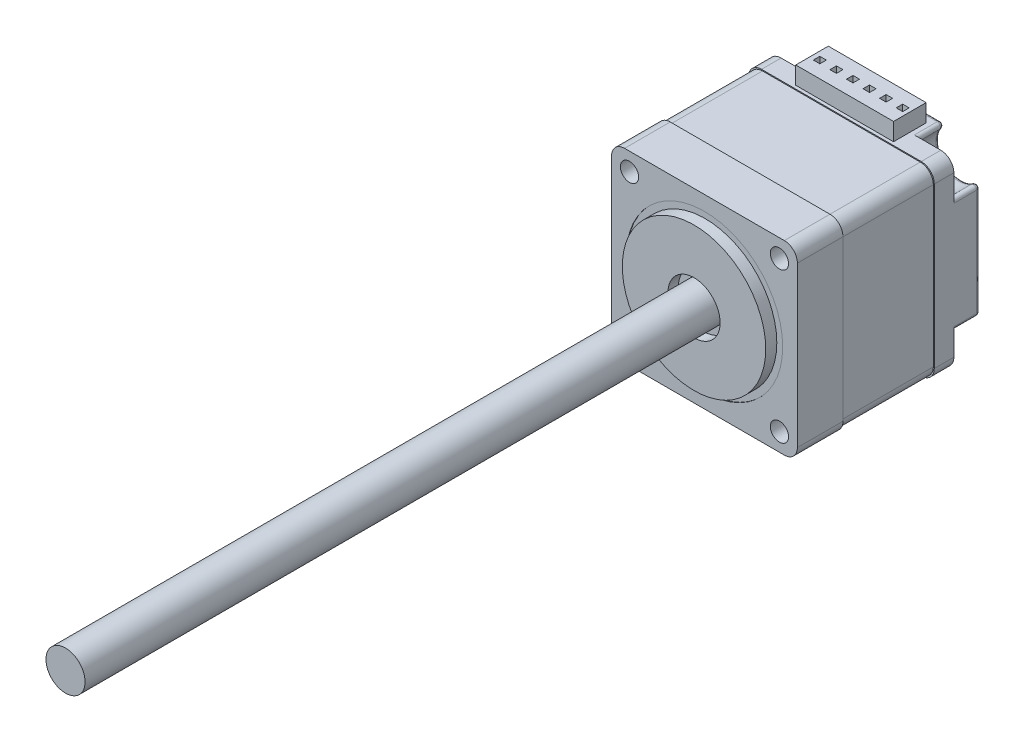
SolidWorks part; units mm, degrees
ref_plane "Front Plane" through (0, 0, 0) normal (0, 0, 1) x (1, 0, 0)
ref_plane "Top Plane" through (0, 0, 0) normal (0, 1, 0) x (1, 0, 0)
ref_plane "Right Plane" through (0, 0, 0) normal (1, 0, 0) x (0, 0, -1)
sketch "Sketch1" plane through (0, 0, 0) normal (0, 0, 1) x (1, 0, 0)
  line L1 (-14.25, 14.25) -> (14.25, 14.25)
  line L2 (-14.25, 14.25) -> (-14.25, -14.25)
  line L3 (-14.25, -14.25) -> (14.25, -14.25)
  line L4 (14.25, 14.25) -> (14.25, -14.25)
  line L5 (-14.25, 14.25) -> (14.25, -14.25) construction
  line L6 (-14.25, -14.25) -> (14.25, 14.25) construction
  point P0 (0, 0)
  dimension "D1" = 28.5
extrude "Boss-Extrude1" add sketch "Sketch1" along normal blind 7
fillet "Fillet1" radius 2 4 edges at (14.25, -14.25, 3.5) (-14.25, -14.25, 3.5) (14.25, 14.25, 3.5) (-14.25, 14.25, 3.5)
sketch "Sketch2" plane through (0, 0, 7) normal (0, 0, 1) x (1, 0, 0)
  circle A0 centre (0, 0) radius 11
  dimension "D1" = 22
extrude "Boss-Extrude2" add sketch "Sketch2" along normal blind 1.6
sketch "Sketch3" plane through (0, 0, 8.6) normal (0, 0, 1) x (1, 0, 0)
  circle A0 centre (0, 0) radius 4
  dimension "D1" = 8
extrude "Cut-Extrude1" cut sketch "Sketch3" against normal blind 1.6
sketch "Sketch4" plane through (0, 0, 7) normal (0, 0, 1) x (1, 0, 0)
  circle A0 centre (0, 0) radius 2.5
  dimension "D1" = 5
extrude "Boss-Extrude3" [suppressed] add sketch "Sketch4" along normal blind 20
sketch "Sketch5" [suppressed] plane through (0, 0, 27) normal (0, 0, 1) x (1, 0, 0)
  line L1 (-2.2, 2) -> (2.2, 2)
  line L2 (-2.2, 2) -> (-2.2, 3)
  line L3 (-2.2, 3) -> (2.2, 3)
  line L4 (2.2, 2) -> (2.2, 3)
  circle A0 centre (0, 0) radius 2.5 construction
  dimension "D1" = 2
  dimension "D2" = 1
  dimension "D3" = 2.2
  dimension "D4" = 4.4
extrude "Cut-Extrude2" [suppressed] cut sketch "Sketch5" against normal blind 20
sketch "Sketch6" plane through (0, 0, 0) normal (0, 0, -1) x (-1, 0, 0)
  line L1 (-14.1, 14.1) -> (14.1, 14.1)
  line L2 (-14.1, 14.1) -> (-14.1, -14.1)
  line L3 (-14.1, -14.1) -> (14.1, -14.1)
  line L4 (14.1, 14.1) -> (14.1, -14.1)
  line L5 (-14.1, 14.1) -> (14.1, -14.1) construction
  line L6 (-14.1, -14.1) -> (14.1, 14.1) construction
  point P0 (0, 0)
  dimension "D1" = 28.2
extrude "Boss-Extrude4" add sketch "Sketch6" along normal blind 14
fillet "Fillet2" radius 2 4 edges at (-14.1, -14.1, -7) (14.1, -14.1, -7) (-14.1, 14.1, -7) (14.1, 14.1, -7)
sketch "Sketch7" plane through (0, 0, -14) normal (0, 0, -1) x (-1, 0, 0)
  line L1 (-14.25, 14.25) -> (14.25, 14.25)
  line L2 (-14.25, 14.25) -> (-14.25, -14.25)
  line L3 (-14.25, -14.25) -> (14.25, -14.25)
  line L4 (14.25, 14.25) -> (14.25, -14.25)
  line L5 (-14.25, 14.25) -> (14.25, -14.25) construction
  line L6 (-14.25, -14.25) -> (14.25, 14.25) construction
  point P0 (0, 0)
  dimension "D1" = 28.5
extrude "Boss-Extrude5" add sketch "Sketch7" along normal blind 7
fillet "Fillet3" radius 2 4 edges at (-14.25, -14.25, -17.5) (14.25, -14.25, -17.5) (-14.25, 14.25, -17.5) (14.25, 14.25, -17.5)
sketch "Sketch8" plane through (0, 14.25, 0) normal (0, 1, 0) x (1, 0, 0)
  line L0 (-12.25, 14) -> (12.25, 14) construction
  line L1 (-7.5, 19.5) -> (7.5, 19.5)
  line L2 (-7.5, 19.5) -> (-7.5, 14.5)
  line L3 (-7.5, 14.5) -> (7.5, 14.5)
  line L4 (7.5, 19.5) -> (7.5, 14.5)
  line L5 (-7.5, 19.5) -> (7.5, 14.5) construction
  line L6 (-7.5, 14.5) -> (7.5, 19.5) construction
  point P0 (0, 17)
  dimension "D1" = 5
  dimension "D2" = 15
  dimension "D3" = 0
  dimension "D4" = 0.5
extrude "Boss-Extrude6" add sketch "Sketch8" along normal blind 2.7
sketch "Sketch9" plane through (0, 0, 7) normal (0, 0, 1) x (1, 0, 0)
  circle A0 centre (-11.5, 11.5) radius 1.4
  circle A1 centre (11.5, 11.5) radius 1.4
  circle A2 centre (11.5, -11.5) radius 1.4
  circle A3 centre (-11.5, -11.5) radius 1.4
  dimension "D1" = 2.8
  dimension "D2" = 23
  dimension "D3" = 23
  dimension "D4" = 23
  dimension "D5" = 23
  dimension "D6" = 11.5
  dimension "D7" = 11.5
  dimension "D8" = 11.5
  dimension "D9" = 11.5
extrude "Cut-Extrude3" cut sketch "Sketch9" against normal blind 42.7
sketch "Sketch10" plane through (0, 0, -21) normal (0, 0, -1) x (-1, 0, 0)
  circle A0 centre (-11.5, 11.5) radius 3.5
  circle A1 centre (11.5, 11.5) radius 3.5
  circle A2 centre (11.5, -11.5) radius 3.5
  circle A3 centre (-11.5, -11.5) radius 3.5
  dimension "D1" = 7
extrude "Cut-Extrude4" cut sketch "Sketch10" against normal blind 4
fillet "Fillet4" radius 0.5 8 edges at (-14.25, 9.3349, -19) (-9.3349, 14.25, -19) (-14.25, -9.3349, -19) (-9.3349, -14.25, -19) (9.3349, -14.25, -19) (14.25, -9.3349, -19) (9.3349, 14.25, -19) (14.25, 9.3349, -19)
fillet "Fillet5" radius 0.5 16 edges at (-13.9839, -8.6348, -21) (-9.0251, -9.0251, -21) (-8.6348, -13.9839, -21) (0, -14.25, -21) (8.6348, -13.9839, -21) (9.0251, -9.0251, -21) (13.9839, -8.6348, -21) (14.25, 0, -21) (13.9839, 8.6348, -21) (9.0251, 9.0251, -21) (8.6348, 13.9839, -21) (0, 14.25, -21) (-8.6348, 13.9839, -21) (-9.0251, 9.0251, -21) (-13.9839, 8.6348, -21) (-14.25, 0, -21)
sketch "Sketch11" plane through (0, 0, 7) normal (0, 0, 1) x (1, 0, 0)
  circle A0 centre (0, 0) radius 11
  circle A1 centre (0, 0) radius 12
  dimension "D1" = 1
extrude "Cut-Extrude5" cut sketch "Sketch11" against normal blind 0.1
sketch "Sketch12" plane through (0, 0, -21) normal (0, 0, -1) x (-1, 0, 0)
  circle A0 centre (0, 0) radius 4
  dimension "D1" = 8
extrude "Cut-Extrude6" cut sketch "Sketch12" against normal blind 2.5
sketch "Sketch13" plane through (0, 0, -18.5) normal (0, 0, -1) x (-1, 0, 0)
  circle A0 centre (0, 0) radius 2.5
  dimension "D1" = 5
extrude "Boss-Extrude7" add sketch "Sketch13" along normal blind 0.5
fillet "Fillet6" radius 0.2 1 edges at (-2.5, 0, -19)
sketch "Sketch14" plane through (0, 16.95, 0) normal (0, 1, 0) x (1, 0, 0)
  line L0 (-7.5, 14.5) -> (7.5, 14.5) construction
  line L1 (-6.8, 17.5) -> (-5.8, 17.5)
  line L2 (-6.8, 17.5) -> (-6.8, 16.5)
  line L3 (-6.8, 16.5) -> (-5.8, 16.5)
  line L4 (-5.8, 17.5) -> (-5.8, 16.5)
  line L5 (-7.5, 19.5) -> (-7.5, 14.5) construction
  line L6 (-3.26, 17.5) -> (-3.26, 16.5)
  line L7 (-4.26, 17.5) -> (-3.26, 17.5)
  line L8 (-4.26, 17.5) -> (-4.26, 16.5)
  line L9 (-4.26, 16.5) -> (-3.26, 16.5)
  line L10 (-0.72, 17.5) -> (-0.72, 16.5)
  line L11 (-1.72, 17.5) -> (-0.72, 17.5)
  line L12 (-1.72, 17.5) -> (-1.72, 16.5)
  line L13 (-1.72, 16.5) -> (-0.72, 16.5)
  line L14 (1.82, 17.5) -> (1.82, 16.5)
  line L15 (0.82, 17.5) -> (1.82, 17.5)
  line L16 (0.82, 17.5) -> (0.82, 16.5)
  line L17 (0.82, 16.5) -> (1.82, 16.5)
  line L18 (4.36, 17.5) -> (4.36, 16.5)
  line L19 (3.36, 17.5) -> (4.36, 17.5)
  line L20 (3.36, 17.5) -> (3.36, 16.5)
  line L21 (3.36, 16.5) -> (4.36, 16.5)
  line L22 (6.9, 17.5) -> (6.9, 16.5)
  line L23 (5.9, 17.5) -> (6.9, 17.5)
  line L24 (5.9, 17.5) -> (5.9, 16.5)
  line L25 (5.9, 16.5) -> (6.9, 16.5)
  dimension "D1" = 1
  dimension "D2" = 1
  dimension "D3" = 2
  dimension "D4" = 0.7
  dimension "D5" = 6
extrude "Cut-Extrude7" cut sketch "Sketch14" against normal blind 5
sketch "Эскиз1" plane through (0, 0, 7) normal (0, 0, 1) x (1, 0, 0)
  circle A0 centre (0, 0) radius 3
  dimension "D1" = 6
extrude "Shaft" add sketch "Эскиз1" along normal blind 98
